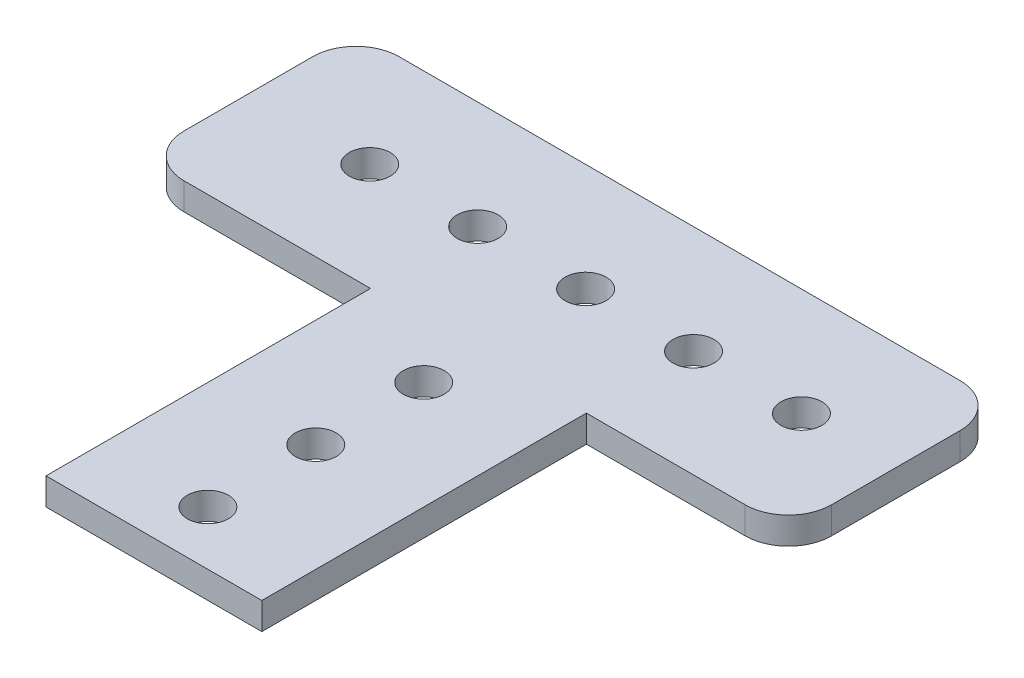
SolidWorks part; units mm, degrees
ref_plane "Front Plane" through (0, 0, 0) normal (0, 0, 1) x (1, 0, 0)
ref_plane "Top Plane" through (0, 0, 0) normal (0, 1, 0) x (1, 0, 0)
ref_plane "Right Plane" through (0, 0, 0) normal (1, 0, 0) x (0, 0, -1)
sketch "Sketch1" plane through (0, 0, 0) normal (0, 1, 0) x (1, 0, 0)
  line L0 (25.4, 50.8958) -> (49.1706, 50.8958)
  line L1 (0, 0) -> (25.4, 0)
  line L2 (0, 0) -> (0, 50.8958)
  line L4 (25.4, 0) -> (25.4, 50.8958)
  line L5 (-27.0294, 50.8958) -> (0, 50.8958)
  line L6 (-27.0294, 50.8958) -> (-27.0294, 76.2)
  line L7 (-27.0294, 76.2) -> (49.1706, 76.2)
  line L8 (49.1706, 50.8958) -> (49.1706, 76.2)
  dimension "D1" = 76.2
  dimension "D2" = 76.2
  dimension "D3" = 25.3042
  dimension "D4" = 25.4
extrude "Boss-Extrude1" add sketch "Sketch1" along normal blind 3.175
fillet "Fillet1" radius 5.08 6 edges at (-27.0294, 1.5875, -50.8958) (0, 1.5875, 0) (25.4, 1.5875, 0) (49.1706, 1.5875, -50.8958) (49.1706, 1.5875, -76.2) (-27.0294, 1.5875, -76.2)
sketch "Sketch2" plane through (0, 3.175, 0) normal (0, 1, 0) x (1, 0, 0)
  line L0 (0, 12.7) -> (25.4, 12.7)
  line L1 (0, 50.8958) -> (0, 5.08) construction
  line L2 (25.4, 5.08) -> (25.4, 50.8958) construction
  line L3 (25.4, 12.7) -> (25.4, 0)
  line L4 (25.4, 0) -> (0, 0)
  line L5 (0, 0) -> (0, 12.7)
  line L8 (-27.0294, 71.12) -> (-27.0294, 55.9758) construction
  line L9 (-285.75, 76.2) -> (158.75, 76.2) construction
  circle A0 centre (12.7, 19.05) radius 2.413
  circle A1 centre (12.7, 31.75) radius 2.413
  circle A2 centre (12.7, 44.45) radius 2.413
  circle A3 centre (-12.6988, 63.5) radius 2.413
  circle A4 centre (0.0012, 63.5) radius 2.413
  circle A5 centre (12.7012, 63.5) radius 2.413
  circle A6 centre (25.4012, 63.5) radius 2.413
  circle A7 centre (38.1012, 63.5) radius 2.413
  dimension "D2" = 4.826
  dimension "D3" = 6.35
  dimension "D6" = 4.826
  dimension "D7" = 14.3307
  dimension "D8" = 12.7
  dimension "D1" = 12.7
  dimension "D4" = 12.7
  dimension "D5" = 3
  dimension "D9" = 5
extrude "Cut-Extrude1" cut sketch "Sketch2" against normal through all
